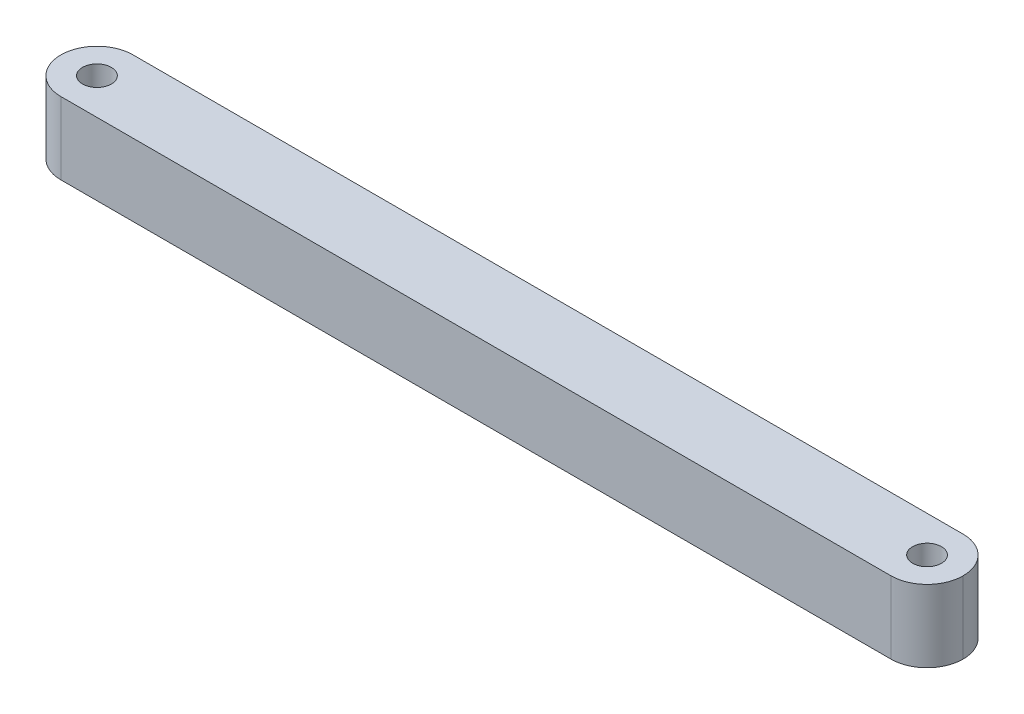
SolidWorks part; units mm, degrees
ref_plane "정면" through (0, 0, 0) normal (0, 0, 1) x (1, 0, 0)
ref_plane "윗면" through (0, 0, 0) normal (0, 1, 0) x (1, 0, 0)
ref_plane "우측면" through (0, 0, 0) normal (1, 0, 0) x (0, 0, -1)
sketch "스케치1" plane through (0, 0, 0) normal (0, 0, 1) x (1, 0, 0)
  line L1 (-62.5, -5) -> (62.5, -5)
  line L2 (-62.5, -5) -> (-62.5, 5)
  line L3 (-62.5, 5) -> (62.5, 5)
  line L4 (62.5, -5) -> (62.5, 5)
  line L5 (-62.5, -5) -> (62.5, 5) construction
  line L6 (-62.5, 5) -> (62.5, -5) construction
  point P0 (0, 0)
  dimension "D1" = 125
  dimension "D2" = 10
extrude "보스-돌출1" add sketch "스케치1" along normal blind 10
fillet "필렛1" radius 5 4 edges at (62.5, 0, 10) (62.5, 0, 0) (-62.5, 0, 0) (-62.5, 0, 10)
sketch "스케치2" plane through (0, 5, 0) normal (0, 1, 0) x (1, 0, 0)
  circle A0 centre (-57.5, -5) radius 2
  circle A1 centre (57.5, -5) radius 2
  dimension "D1" = 4
extrude "컷-돌출1" cut sketch "스케치2" against normal blind 10
